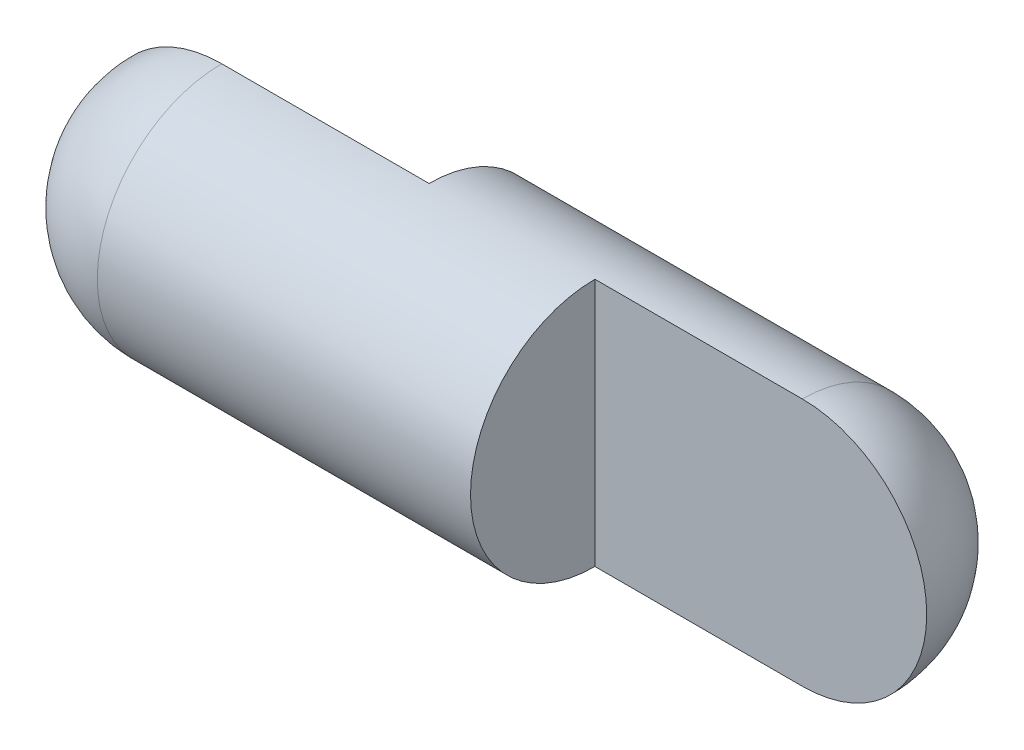
SolidWorks part; units mm, degrees
ref_plane "Front Plane" through (0, 0, 0) normal (0, 0, 1) x (1, 0, 0)
ref_plane "Top Plane" through (0, 0, 0) normal (0, 1, 0) x (1, 0, 0)
ref_plane "Right Plane" through (0, 0, 0) normal (1, 0, 0) x (0, 0, -1)
sketch "Sketch1" plane through (0, 0, 0) normal (0, 0, 1) x (1, 0, 0)
  line L0 (0, -652.3429) -> (0, 1677.7917) construction
  line L6 (0, 75) -> (225, 75)
  line L7 (-75, -11.1998) -> (-75, 194.1976) construction
  line L8 (425, -114.9576) -> (425, 108.5359) construction
  line L9 (125, 108.5754) -> (125, -133.5084) construction
  line L10 (225, 134.1093) -> (225, -152.9674) construction
  line L11 (125, 0) -> (125, -75)
  line L12 (125, -75) -> (350, -75)
  line L14 (225, 0) -> (225, 75)
  line L15 (-196.8051, 75) -> (443.2966, 75) construction
  line L16 (338.357, -75) -> (-116.9241, -75) construction
  line L17 (-97.7961, 0) -> (388.6112, 0) construction
  line L18 (350, -104.6307) -> (350, 52.0676) construction
  line L20 (425, 0) -> (125, 0)
  line L21 (-75, 0) -> (225, 0)
  arc A4 (0, 75) -> (-75, 0) centre (0, 0) ccw
  arc A6 (350, -75) -> (425, 0) centre (350, 0) ccw
  point P13 (0, 0)
  dimension "D1" = 75
  dimension "D2" = 150
  dimension "D3" = 500
  dimension "D4" = 225
  dimension "D5" = 225
revolve "Revolve1" add sketch "Sketch1" angle 180 about L17
ref_axis "Axis1" through (0, 0, -82.5) along (0, 0, 1)
revolve "Revolve2" add sketch "Sketch1<4>" angle 180 about L17 region at (267.4459, -36.3238, 0)
sketch "Sketch1<4>" plane through (0, 0, 0) normal (0, 0, 1) x (1, 0, 0) same geometry as "Sketch1"
ref_plane "Plane1" through (350, 0, 0) normal (1, 0, 0) x (0, 0, -1)
ref_axis "Axis2" through (350, 0, -164.5331) along (0, 0, 1)
equation "\"link2_diameter\"=150"
equation "\"link2_length\"=300"
equation "\"link3_diameter\"=150"
equation "\"link3_length\"=150"
equation "\"link4_diameter\"=150"
equation "\"link4_length\"=150"
equation "\"link5_diameter\"=150"
equation "\"link5_length\"=200"
equation "\"end_effector_diameter\"=150"
equation "\"end_effector_length\"=150"
equation "\"base_link_diameterA\"=200"
equation "\"base_link_diameterB\"=150"
equation "\"base_link_length\"=150"
equation "\"base_link_lengthA\"=50"
equation "\"link1_diameter\"=150"
equation "\"link1_length\"=150"
equation "\"D1@Sketch1\"=\"link2_diameter\"/2"
